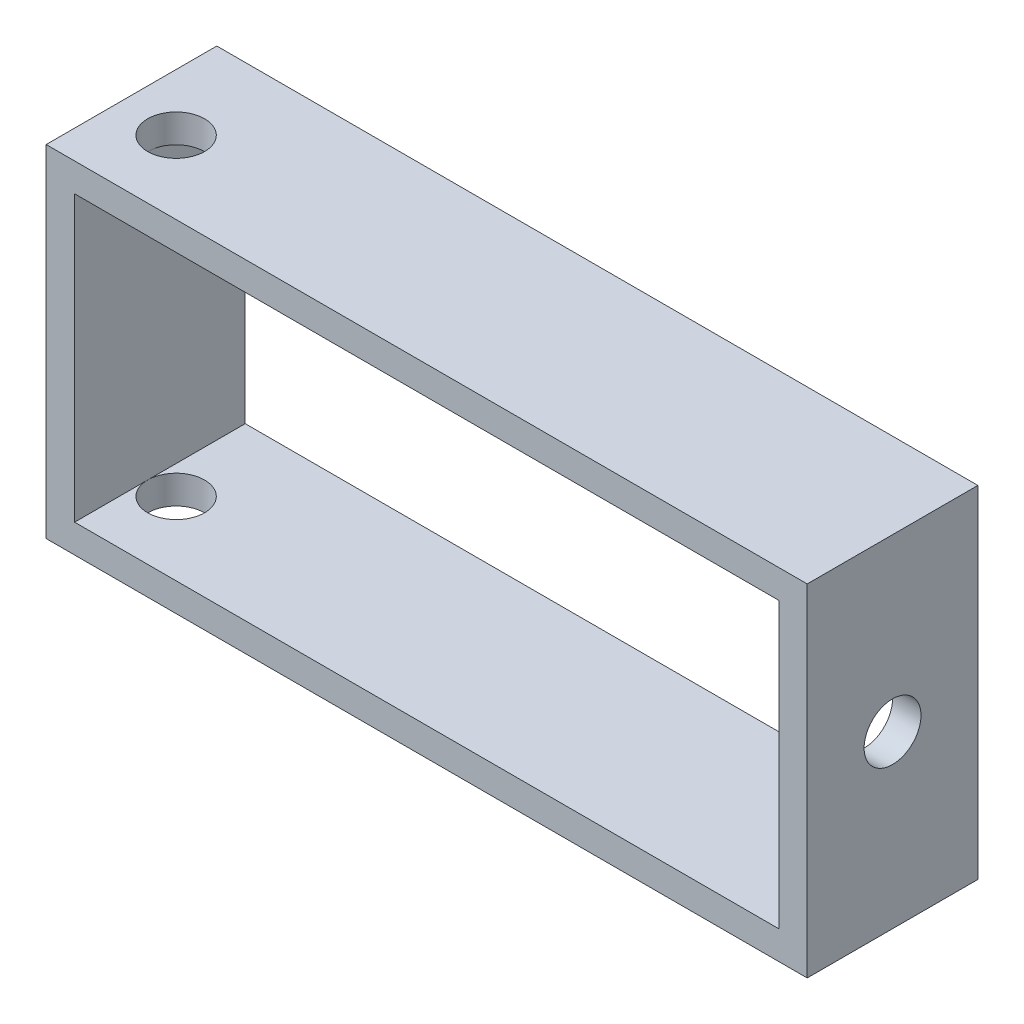
SolidWorks part; units mm, degrees
ref_plane "Alzado" through (0, 0, 0) normal (0, 0, 1) x (1, 0, 0)
ref_plane "Planta" through (0, 0, 0) normal (0, 1, 0) x (1, 0, 0)
ref_plane "Vista lateral" through (0, 0, 0) normal (1, 0, 0) x (0, 0, -1)
sketch "Croquis1" plane through (0, 0, 0) normal (0, 1, 0) x (1, 0, 0)
  line L1 (-36.5645, -5.3571) -> (97.2355, -5.3571)
  line L2 (-36.5645, -5.3571) -> (-36.5645, 24.6429)
  line L3 (-36.5645, 24.6429) -> (97.2355, 24.6429)
  line L4 (97.2355, -5.3571) -> (97.2355, 24.6429)
  circle A0 centre (-26.5645, 7.4948) radius 5
  dimension "D3" = 10
  dimension "D1" = 30
  dimension "D2" = 133.8
  dimension "D4" = 10
extrude "Saliente-Extruir1" add sketch "Croquis1" along normal blind 60
sketch "Croquis2" plane through (0, 0, 5.3571) normal (0, 0, 1) x (1, 0, 0)
  line L0 (-36.5645, 0) -> (97.2355, 0) construction
  line L1 (-31.5645, 55) -> (92.2355, 55)
  line L2 (-31.5645, 55) -> (-31.5645, 5)
  line L3 (-31.5645, 5) -> (92.2355, 5)
  line L4 (92.2355, 55) -> (92.2355, 5)
  line L5 (-36.5645, 60) -> (-36.5645, 0) construction
  dimension "D1" = 50
  dimension "D2" = 123.8
  dimension "D3" = 5
  dimension "D4" = 5
extrude "Cortar-Extruir1" cut sketch "Croquis2" against normal through all
ref_axis "z3" through (-26.5645, 97.6754, -7.4948) along (0, -1, 0)
sketch "Croquis3" plane through (97.2355, 0, 0) normal (1, 0, 0) x (0, 0, -1)
  line L0 (-5.3571, 60) -> (-5.3571, 0) construction
  line L1 (-5.3571, 0) -> (24.6429, 0) construction
  circle A0 centre (9.6429, 30) radius 5
  dimension "D1" = 10
  dimension "D2" = 15
  dimension "D3" = 30
extrude "Cortar-Extruir2" cut sketch "Croquis3" against normal blind 10
ref_axis "z4" through (69.0449, 30, -9.6429) along (1, 0, 0)
